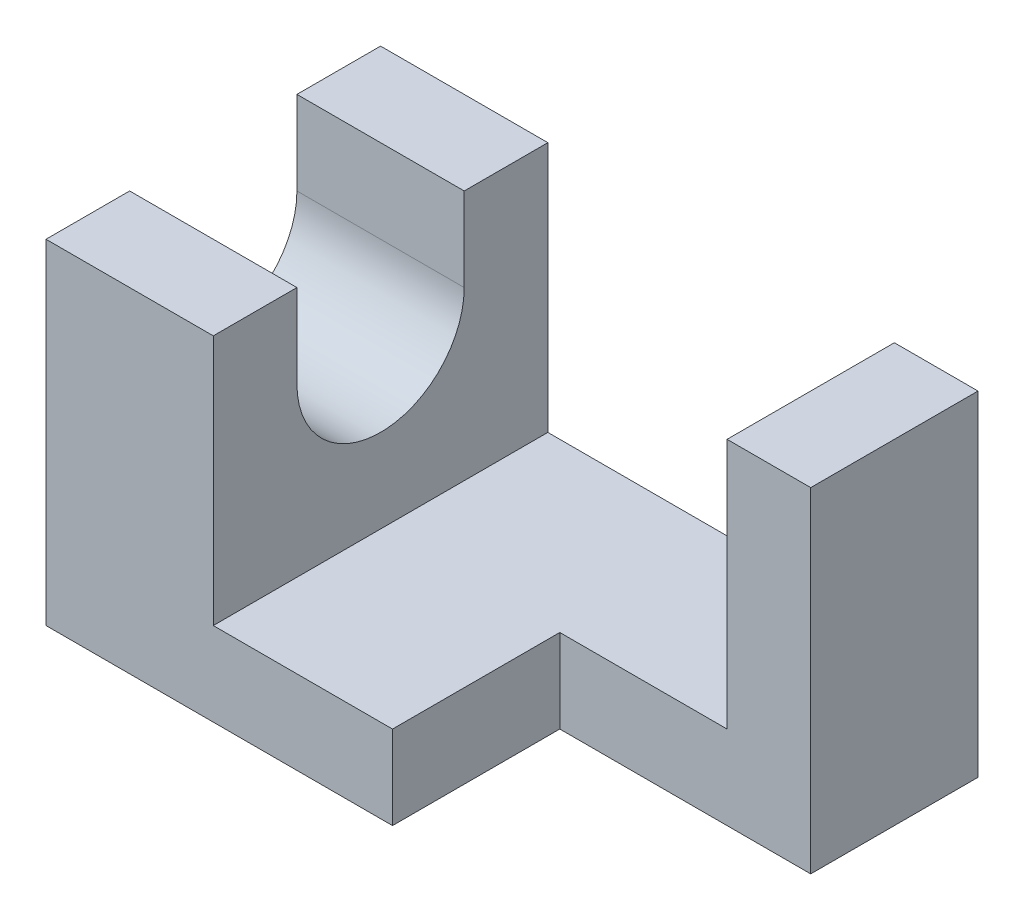
SolidWorks part; units mm, degrees
ref_plane "Front Plane" through (0, 0, 0) normal (0, 0, 1) x (1, 0, 0)
ref_plane "Top Plane" through (0, 0, 0) normal (0, 1, 0) x (1, 0, 0)
ref_plane "Right Plane" through (0, 0, 0) normal (1, 0, 0) x (0, 0, -1)
sketch "Sketch1" plane through (0, 0, 0) normal (0, 1, 0) x (1, 0, 0)
  line L0 (0, 0) -> (-29, 0)
  line L1 (-29, 0) -> (-29, 28)
  line L2 (-29, 28) -> (21, 28)
  line L3 (21, 28) -> (21, 14)
  line L4 (21, 14) -> (0, 14)
  line L5 (0, 14) -> (0, 0)
  line L6 (14, 28) -> (14, 14)
  line L7 (-15, 28) -> (-15, 0)
  point P11 (-15, 3.37)
  dimension "D1" = 28
  dimension "D2" = 50
  dimension "D3" = 21
  dimension "D4" = 14
  dimension "D5" = 7
  dimension "D6" = 14
extrude "Boss-Extrude1" add sketch "Sketch1" along normal blind 7 contours L2 L7 L0 L5 L4 L6 region at (-2.8864, 0, -16.2273)
extrude "Boss-Extrude2" add sketch "Sketch1<3>" along normal blind 28 contours L7 L2 L1 L0 | L2 L6 L4 L3 region at (-22, 0, -14) region at (17.5, 0, -21)
sketch "Sketch1<3>" plane through (0, 0, 0) normal (0, 1, 0) x (1, 0, 0) same geometry as "Sketch1"
sketch "Sketch2" plane through (-29, 0, 0) normal (-1, 0, 0) x (0, 0, 1)
  line L0 (-14, 28) -> (-14, 0) construction
  line L1 (0, 0) -> (-28, 0) construction
  line L2 (-21, 28) -> (-21, 21)
  line L3 (0, 28) -> (-28, 28) construction
  line L4 (-7, 28) -> (-7, 21)
  arc A0 (-21, 21) -> (-7, 21) centre (-14, 21) ccw
  point P11 (0, 0)
  line M4 (0, 28) -> (-28, 28)
  dimension "D1" = 7
  dimension "D2" = 21
extrude "Cut-Extrude1" cut sketch "Sketch2" against normal blind 28 and the other way through all contours L0 L2 A0 M4 | L0 A0 L4 M4 region at (-29, 21.6534, -10.7328) region at (-29, 21.6534, -17.2672)
